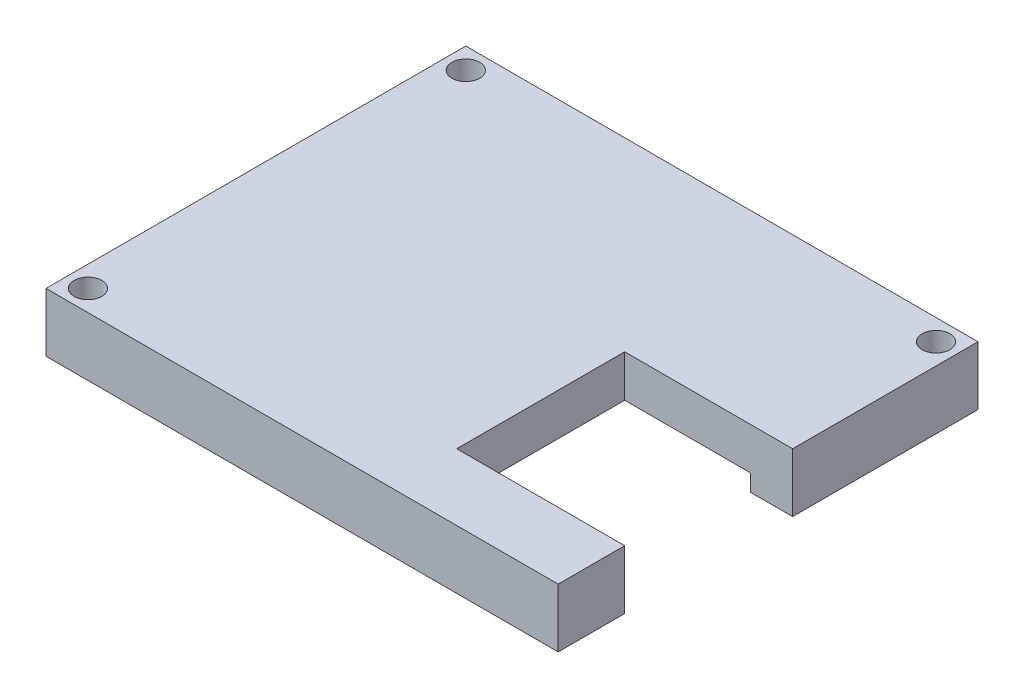
SolidWorks part; units mm, degrees
ref_plane "Front Plane" through (0, 0, 0) normal (0, 0, 1) x (1, 0, 0)
ref_plane "Top Plane" through (0, 0, 0) normal (0, 1, 0) x (1, 0, 0)
ref_plane "Right Plane" through (0, 0, 0) normal (1, 0, 0) x (0, 0, -1)
sketch "Sketch1" plane through (0, 0, 0) normal (0, 1, 0) x (1, 0, 0)
  line L1 (0, 0) -> (64.77, 0)
  line L2 (0, 0) -> (0, 50.8)
  line L3 (0, 50.8) -> (64.77, 50.8)
  line L4 (64.77, 0) -> (64.77, 50.8)
  line L5 (71.12, 58.2951) -> (-6.35, 58.2951)
  line L6 (71.12, 58.2951) -> (71.12, -5.2049)
  line L7 (71.12, -5.2049) -> (-6.35, -5.2049)
  line L8 (-6.35, 58.2951) -> (-6.35, -5.2049)
  line L9 (71.12, 58.2951) -> (-6.35, -5.2049) construction
  line L10 (71.12, -5.2049) -> (-6.35, 58.2951) construction
  point P5 (32.385, 26.5451)
  dimension "D1" = 64.77
  dimension "D2" = 50.8
  dimension "D3" = 63.5
  dimension "D4" = 77.47
extrude "Boss-Extrude1" add sketch "Sketch1" along normal blind 6.35 contours L1 L4 L3 L2 | L5 L8 L7 L6 L4 L1 L2 L3 region at (32.385, 0, -25.4) region at (70.1183, 0, -26.5451)
extrude "Boss-Extrude2" add sketch "Sketch1<3>" against normal blind 2.54
sketch "Sketch1<3>" plane through (0, 0, 0) normal (0, 1, 0) x (1, 0, 0) same geometry as "Sketch1"
sketch "Sketch2" plane through (0, -2.54, 0) normal (0, -1, 0) x (1, 0, 0)
  line L0 (71.12, 5.2049) -> (71.12, -58.2951) construction
  line L1 (71.12, -4.8566) -> (45.72, -4.8566)
  line L2 (71.12, -4.8566) -> (71.12, -30.2566)
  line L3 (71.12, -30.2566) -> (45.72, -30.2566)
  line L4 (45.72, -4.8566) -> (45.72, -30.2566)
  dimension "D1" = 25.4
  dimension "D2" = 25.4
extrude "Cut-Extrude1" cut sketch "Sketch2" against normal blind 12.7
sketch "Sketch3" plane through (0, -2.54, 0) normal (0, -1, 0) x (1, 0, 0)
  line L0 (-6.35, -58.2951) -> (-6.35, 5.2049) construction
  line L1 (-6.35, 5.2049) -> (71.12, 5.2049) construction
  line L2 (71.12, -58.2951) -> (-6.35, -58.2951) construction
  line L3 (71.12, -30.2566) -> (71.12, -58.2951) construction
  circle A0 centre (-3.175, 2.0299) radius 2.1
  circle A1 centre (-3.175, -55.1201) radius 2.1
  circle A2 centre (67.945, -55.1201) radius 2.1
  point P6 (-2.2066, -54.0929)
  point P7 (67.0629, -53.9995)
  point P8 (-2.1904, 1.3061)
  point P13 (0.9609, 3.4811)
  point P16 (3.0146, 3.1203)
  dimension "D1" = 4.2
  dimension "D2" = 3.175
  dimension "D3" = 3.175
  dimension "D4" = 3.175
  dimension "D5" = 3.175
extrude "Cut-Extrude2" cut sketch "Sketch3" against normal blind 12.7
